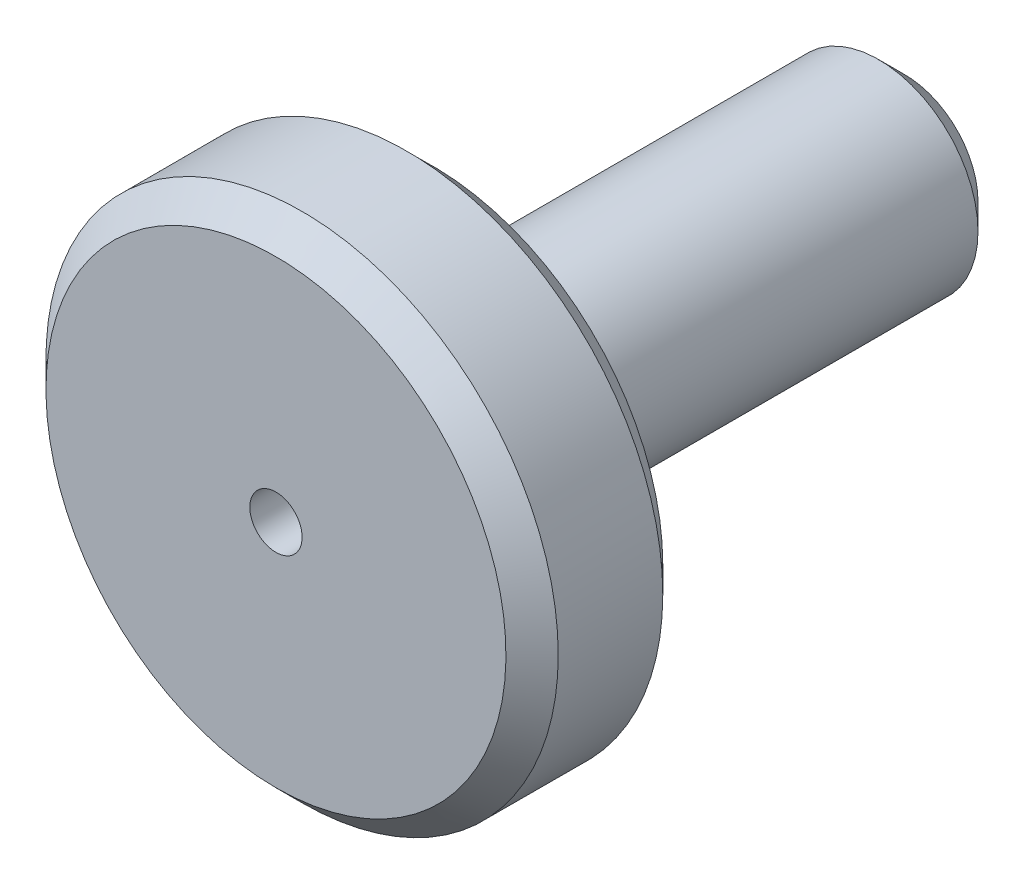
SolidWorks part; units mm, degrees
ref_plane "Front Plane" through (0, 0, 0) normal (0, 0, 1) x (1, 0, 0)
ref_plane "Top Plane" through (0, 0, 0) normal (0, 1, 0) x (1, 0, 0)
ref_plane "Right Plane" through (0, 0, 0) normal (1, 0, 0) x (0, 0, -1)
sketch "Sketch1" plane through (0, 0, 0) normal (0, 0, 1) x (1, 0, 0)
  circle A0 centre (0, 52.925) radius 4.9
  circle A1 centre (0, 52.925) radius 1.9
  dimension "D1" = 3.8
  dimension "D2" = 9.8
extrude "Boss-Extrude1" add sketch "Sketch1" along normal up to surface (3 mm away) contours A0 A1 | A1 region at (-4.7614, 52.925, 0) region at (0, 52.925, 0)
extrude "Boss-Extrude2" add sketch "Sketch1<4>" against normal blind 9.03 contours A1 region at (0, 52.925, 0)
sketch "Sketch1<4>" plane through (0, 0, 0) normal (0, 0, 1) x (1, 0, 0) same geometry as "Sketch1"
fillet "Fillet1" radius 0.5 1 edges at (1.9, 52.925, 0)
chamfer "Chamfer1" distance 0.5 angle 45 3 edges at (0, 48.025, 3) (1.9, 52.925, -9.03) (4.9, 52.925, 0)
sketch "Sketch2" plane through (0, 0, 3) normal (0, 0, 1) x (1, 0, 0)
  circle A0 centre (0, 52.925) radius 0.5
  dimension "D1" = 1
extrude "Cut-Extrude1" cut sketch "Sketch2" against normal up to next
